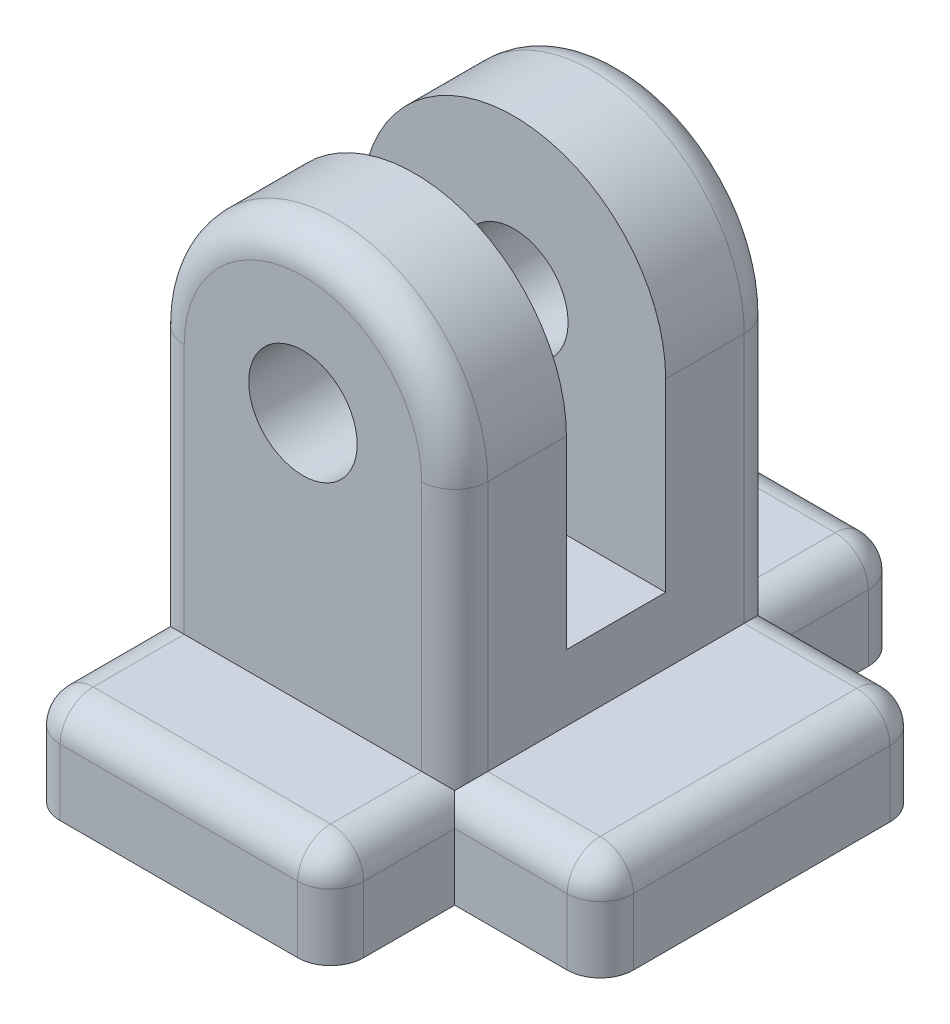
SolidWorks part; units mm, degrees
ref_plane "Front Plane" through (0, 0, 0) normal (0, 0, 1) x (1, 0, 0)
ref_plane "Top Plane" through (0, 0, 0) normal (0, 1, 0) x (1, 0, 0)
ref_plane "Right Plane" through (0, 0, 0) normal (1, 0, 0) x (0, 0, -1)
sketch "Sketch1" plane through (0, 0, 0) normal (0, 0, 1) x (1, 0, 0)
  line L0 (-4.5875, 0) -> (-4.5875, -10.5875)
  line L1 (-4.5875, -10.5875) -> (8.9875, -10.5875)
  line L2 (8.9875, -10.5875) -> (8.9875, -7.5875)
  line L3 (8.9875, -7.5875) -> (4.5875, -7.5875)
  line L4 (4.5875, -7.5875) -> (4.5875, 0)
  circle A0 centre (0, 0) radius 1.6375
  arc A1 (4.5875, 0) -> (-4.5875, 0) centre (0, 0) ccw
  dimension "D2" = 3.275
  dimension "D3" = 9.175
  dimension "D1" = 4.4
  dimension "D4" = 7.5875
  dimension "D5" = 3
extrude "Boss-Extrude1" add sketch "Sketch1" along normal blind 9.75
sketch "Sketch2" plane through (0, 0, 9.75) normal (0, 0, 1) x (1, 0, 0)
  line L1 (4.5875, -7.5875) -> (-4.5875, -7.5875)
  line L2 (4.5875, -7.5875) -> (4.5875, -10.5875)
  line L3 (4.5875, -10.5875) -> (-4.5875, -10.5875)
  line L4 (-4.5875, -7.5875) -> (-4.5875, -10.5875)
extrude "Boss-Extrude2" add sketch "Sketch2" along normal blind 3.75 and the other way blind 13.5
fillet "Fillet1" radius 1 13 edges at (4.5875, -9.0875, -3.75) (-4.5875, -9.0875, -3.75) (0, -7.5875, -3.75) (0, -7.5875, 13.5) (4.5875, -7.5875, 11.625) (4.5875, -7.5875, -1.875) (-4.5875, -7.5875, 11.625) (-4.5875, -7.5875, -1.875) (8.9875, -9.0875, 9.75) (8.9875, -7.5875, 4.875) (8.9875, -9.0875, 0) (4.5875, -9.0875, 13.5) (-4.5875, -9.0875, 13.5)
fillet "Fillet2" radius 1 10 edges at (4.5875, -3.7938, 0) (-4.5875, -4.2938, 0) (8.6946, -7.8804, 0.2929) (8.6946, -7.8804, 9.4571) (4.5875, -3.7938, 9.75) (-4.5875, -4.2938, 9.75) (0, 4.5875, 0) (6.2875, -7.5875, 0) (6.2875, -7.5875, 9.75) (0, 4.5875, 9.75)
sketch "Sketch3" plane through (0, 0, 0) normal (0, 0, -1) x (-1, 0, 0)
  line L0 (-4.875, 0) -> (-4.875, -5.5875)
  line L1 (-4.875, -5.5875) -> (4.875, -5.5875)
  line L2 (4.875, -5.5875) -> (4.875, 0)
  line L3 (-3.5875, -7.5875) -> (3.5875, -7.5875) construction
  arc A0 (4.875, 0) -> (-4.875, 0) centre (0, 0) ccw
  dimension "D1" = 9.75
  dimension "D2" = 2
extrude "Cut-Extrude1" cut sketch "Sketch3" against normal blind 3 from offset 3.375 offset against normal yes
